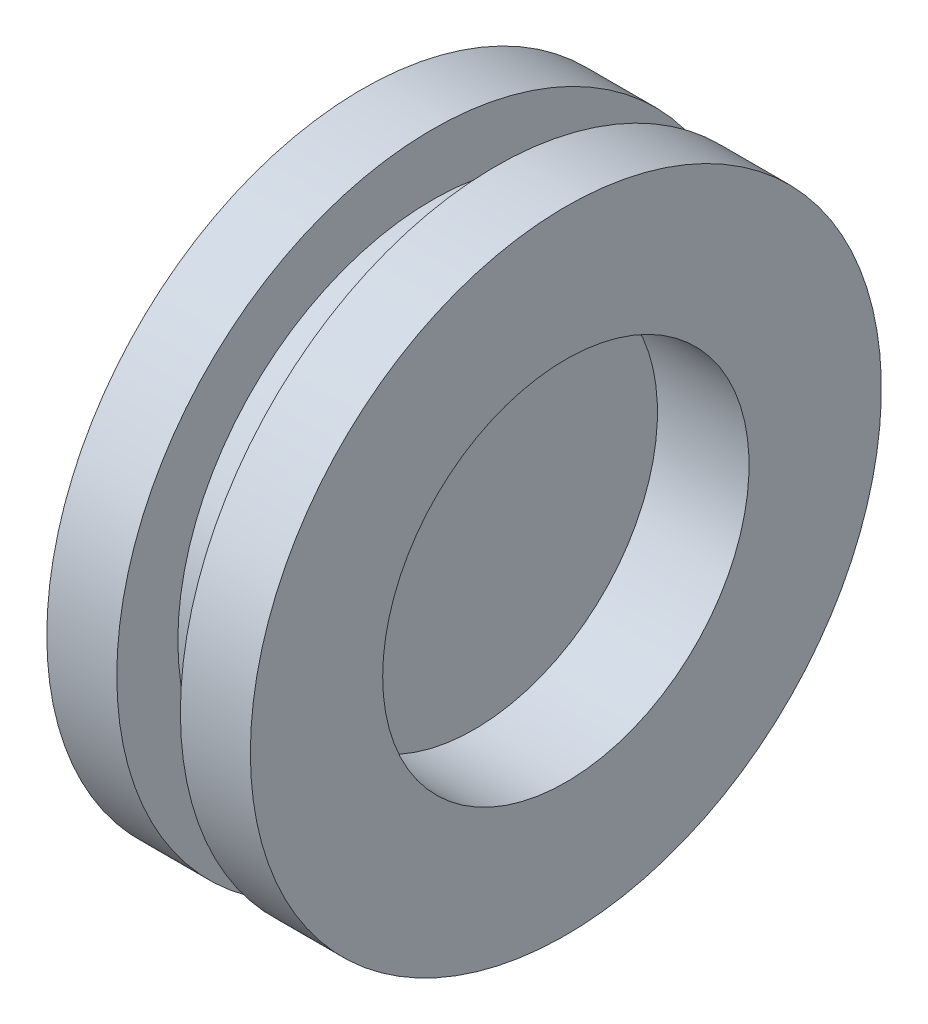
SolidWorks part; units mm, degrees
material "NBR"
ref_plane "Front" through (0, 0, 0) normal (0, 0, 1) x (1, 0, 0)
ref_plane "Top" through (0, 0, 0) normal (0, 1, 0) x (1, 0, 0)
ref_plane "Right" through (0, 0, 0) normal (1, 0, 0) x (0, 0, -1)
ref_axis "Axis1" through (0, 0, 55) along (0, 0, -1)
sketch "Sketch1" plane through (0, 0, 0) normal (0, 0, 1) x (1, 0, 0)
  line L0 (-3.81, 0) -> (3.81, 0) construction
  line L1 (-0.254, 0) -> (0.254, 0)
  line L2 (0.254, 0) -> (0.254, 4.572)
  line L3 (0.254, 4.572) -> (2.54, 4.572)
  line L4 (2.54, 4.572) -> (2.54, 7.874)
  line L5 (2.54, 7.874) -> (0.7937, 7.874)
  line L6 (0.7937, 7.874) -> (0.7937, 6.35)
  line L7 (0.7937, 6.35) -> (-0.7937, 6.35)
  line L8 (-0.7937, 6.35) -> (-0.7937, 7.874)
  line L9 (-0.7937, 7.874) -> (-2.54, 7.874)
  line L10 (-2.54, 7.874) -> (-2.54, 4.572)
  line L11 (-2.54, 4.572) -> (-0.254, 4.572)
  line L12 (-0.254, 4.572) -> (-0.254, 0)
  line L13 (0, 0) -> (0, 6.35) construction
  point P4 (0, 0)
  dimension "D1" = 7.62
  dimension "D2" = 1.5875
  dimension "D3" = 5.08
  dimension "D4" = 0.508
  dimension "D5" = 6.35
  dimension "D6" = 1.524
  dimension "D7" = 4.572
revolve "Revolve1" add sketch "Sketch1" angle 360 about L0
